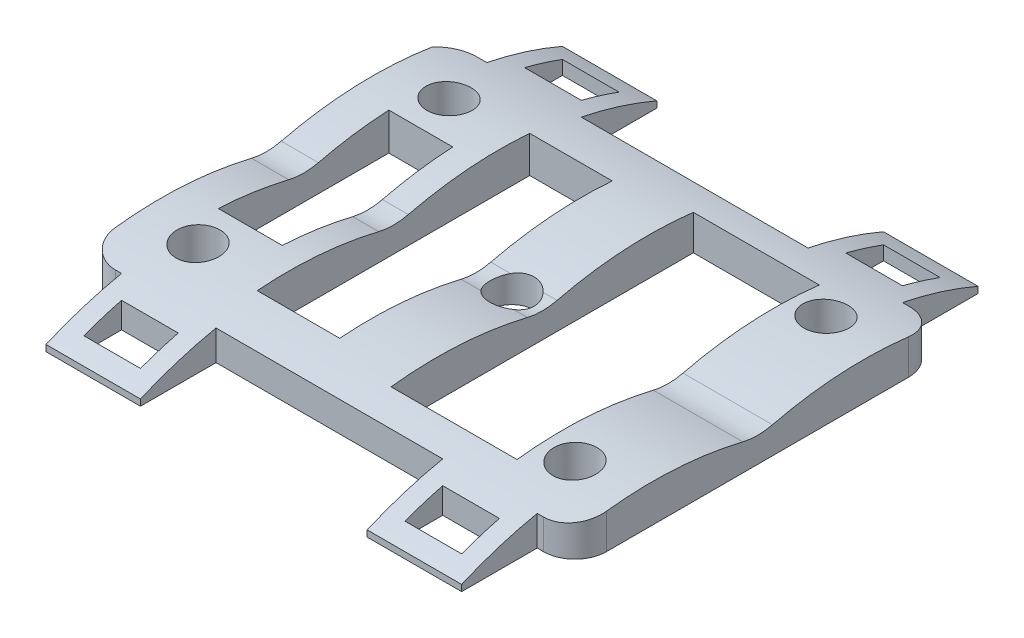
SolidWorks part; units mm, degrees
ref_plane "Front Plane" through (0, 0, 0) normal (0, 0, 1) x (1, 0, 0)
ref_plane "Top Plane" through (0, 0, 0) normal (0, 1, 0) x (1, 0, 0)
ref_plane "Right Plane" through (0, 0, 0) normal (1, 0, 0) x (0, 0, -1)
sketch "Sketch1" plane through (0, 0, 0) normal (0, 1, 0) x (1, 0, 0)
  line L0 (-33, -29) -> (-33, -41) construction
  line L5 (-33, -41) -> (-18, -41) construction
  line L6 (-18, -29) -> (-18, -41) construction
  line L7 (18, -29) -> (18, -41) construction
  line L8 (33, -41) -> (18, -41) construction
  line L9 (33, -29) -> (33, -41) construction
  line L10 (18, 29) -> (18, 41) construction
  line L11 (33, 41) -> (18, 41) construction
  line L12 (33, 29) -> (33, 41) construction
  line L13 (-33, 29) -> (-33, 41) construction
  line L14 (-33, 41) -> (-18, 41) construction
  line L15 (-18, 29) -> (-18, 41) construction
  line L16 (-34.5218, 29) -> (-33, 29) construction
  line L17 (-33, 29) -> (-18, 29) construction
  line L18 (-18, 29) -> (18, 29) construction
  line L19 (18, 29) -> (33, 29) construction
  line L20 (33, 29) -> (34, 29) construction
  line L21 (-34, -29) -> (-33, -29) construction
  line L34 (-18, -29) -> (-33, -29) construction
  line L35 (-18, -29) -> (18, -29) construction
  line L36 (33, -29) -> (18, -29) construction
  line L38 (33, -29) -> (34, -29) construction
  line L40 (-33, -29) -> (-33, -41)
  line L44 (-33, -41) -> (-18, -41)
  line L45 (-18, -29) -> (-18, -41)
  line L49 (18, -29) -> (18, -41)
  line L60 (33, -41) -> (18, -41)
  line L94 (33, -29) -> (33, -41)
  line L95 (18, 29) -> (18, 41)
  line L96 (33, 41) -> (18, 41)
  line L97 (33, 29) -> (33, 41)
  line L98 (-33, 29) -> (-33, 41)
  line L99 (-33, 41) -> (-18, 41)
  line L100 (-18, 29) -> (-18, 41)
  line L101 (-34.5218, 29) -> (-33, 29)
  line L102 (-33, 29) -> (-18, 29)
  line L103 (-18, 29) -> (18, 29)
  line L104 (18, 29) -> (33, 29)
  line L105 (33, 29) -> (34, 29)
  line L106 (-34, -29) -> (-33, -29)
  line L107 (-18, -29) -> (-33, -29)
  line L108 (-18, -29) -> (18, -29)
  line L109 (33, -29) -> (18, -29)
  line L110 (33, -29) -> (34, -29)
  line L111 (-39, -24) -> (-39, 26.2238)
  line L112 (39, -24) -> (39, 24)
  line L113 (-30, -32) -> (-30, -38) construction
  line L114 (-30, -38) -> (-21, -38) construction
  line L115 (-21, -32) -> (-21, -38) construction
  line L116 (-30, -32) -> (-21, -32) construction
  line L117 (21, -32) -> (21, -38) construction
  line L118 (30, -38) -> (21, -38) construction
  line L119 (30, -32) -> (21, -32) construction
  line L120 (30, -32) -> (30, -38) construction
  line L121 (-30, 32) -> (-21, 32) construction
  line L122 (-30, 32) -> (-30, 38) construction
  line L123 (-30, 38) -> (-21, 38) construction
  line L124 (-21, 32) -> (-21, 38) construction
  line L125 (21, 32) -> (21, 38) construction
  line L126 (30, 32) -> (21, 32) construction
  line L127 (30, 32) -> (30, 38) construction
  line L128 (30, 38) -> (21, 38) construction
  line L129 (-30, -32) -> (-30, -38)
  line L130 (-30, -38) -> (-21, -38)
  line L131 (-21, -32) -> (-21, -38)
  line L132 (-30, -32) -> (-21, -32)
  line L133 (21, -32) -> (21, -38)
  line L134 (30, -38) -> (21, -38)
  line L135 (30, -32) -> (21, -32)
  line L136 (30, -32) -> (30, -38)
  line L137 (-30, 32) -> (-21, 32)
  line L138 (-30, 32) -> (-30, 38)
  line L139 (-30, 38) -> (-21, 38)
  line L140 (-21, 32) -> (-21, 38)
  line L141 (21, 32) -> (21, 38)
  line L142 (30, 32) -> (21, 32)
  line L143 (30, 32) -> (30, 38)
  line L144 (30, 38) -> (21, 38)
  arc A0 (-34.5218, 29) -> (-39.3044, 25.4583) centre (-34.5218, 24) ccw construction
  arc A1 (39, 24) -> (34, 29) centre (34, 24) ccw construction
  arc A2 (-39, -24) -> (-34, -29) centre (-34, -24) ccw construction
  arc A3 (34, -29) -> (39, -24) centre (34, -24) ccw construction
  arc A6 (-34.5218, 29) -> (-39, 26.2238) centre (-34.5218, 24) ccw
  arc A7 (39, 24) -> (34, 29) centre (34, 24) ccw
  arc A8 (-39, -24) -> (-34, -29) centre (-34, -24) ccw
  arc A9 (34, -29) -> (39, -24) centre (34, -24) ccw
extrude "Boss-Extrude1" add sketch "Sketch1" along normal blind 8 contours L44 | L110 A9 L112 A7 L105 L104 L103 L102 L101 A6 L111 A8 L106 L107 L108 L109 | L45 L107 L40 L44 L129 L132 L131 L130 | L94 L109 L49 L60 L135 L136 L134 L133 | L95 L104 L97 L96 L144 L143 L142 L141 | L98 L102 L100 L99 L140 L137 L138 L139 region at (-25.5, 0, 29.1921) region at (-0.0153, 0, -0.011) region at (25.5, 0, 29.1921) region at (-32.8079, 0, -35) region at (18.1921, 0, -35)
sketch "Sketch7" plane through (0, 0, 0) normal (0, -1, 0) x (1, 0, 0)
  circle A0 centre (-29.9289, 19.9289) radius 3.5
  circle A1 centre (29.9289, 19.9289) radius 3.5
  circle A2 centre (-29.9289, -19.9289) radius 3.5
  circle A3 centre (29.9289, -19.9289) radius 3.5
  circle A4 centre (-29.9289, 19.9289) radius 2.5 construction
  circle A5 centre (0, 0) radius 3.5
  dimension "D1" = 1
extrude "Cut-Extrude6" cut sketch "Sketch7" against normal through all
sketch "Sketch8" plane through (0, 0, 0) normal (0, -1, 0) x (1, 0, 0)
  line L0 (-23.942, 12.539) -> (-32.0968, -12.539) construction
  line L1 (-23.942, 12.539) -> (-32.0968, 12.539) construction
  line L2 (-23.942, 12.539) -> (-23.942, -12.539) construction
  line L3 (-23.942, -12.539) -> (-32.0968, -12.539) construction
  line L4 (-32.0968, 12.539) -> (-32.0968, -12.539) construction
  line L5 (-23.942, 12.539) -> (-32.0968, -12.539) construction
  line L6 (-23.942, -12.539) -> (-32.0968, 12.539) construction
  line L7 (5.7951, -23) -> (23.7951, 23) construction
  line L8 (-6.7226, 20.6351) -> (-17.8204, 20.6351) construction
  line L9 (-6.7226, 20.6351) -> (-6.7226, -20.6351) construction
  line L10 (-6.7226, -20.6351) -> (-17.8204, -20.6351) construction
  line L11 (-17.8204, 20.6351) -> (-17.8204, -20.6351) construction
  line L12 (-6.7226, 20.6351) -> (-17.8204, -20.6351) construction
  line L13 (-6.7226, -20.6351) -> (-17.8204, 20.6351) construction
  line L14 (23.7951, 23) -> (5.7951, 23) construction
  line L15 (23.7951, 23) -> (23.7951, -23) construction
  line L16 (23.7951, -23) -> (5.7951, -23) construction
  line L17 (5.7951, 23) -> (5.7951, -23) construction
  line L18 (23.7951, 23) -> (5.7951, -23) construction
  line L19 (23.7951, -23) -> (5.7951, 23) construction
  line L20 (24.7951, -24) -> (4.7951, -24)
  line L21 (4.7951, 24) -> (4.7951, -24)
  line L22 (24.7951, 24) -> (4.7951, 24)
  line L23 (24.7951, 24) -> (24.7951, -24)
  line L24 (-5.7226, -21.6351) -> (-18.8204, -21.6351)
  line L25 (-18.8204, 21.6351) -> (-18.8204, -21.6351)
  line L26 (-5.7226, 21.6351) -> (-18.8204, 21.6351)
  line L27 (-5.7226, 21.6351) -> (-5.7226, -21.6351)
  line L28 (-22.942, -13.539) -> (-33.0968, -13.539)
  line L29 (-33.0968, 13.539) -> (-33.0968, -13.539)
  line L30 (-22.942, 13.539) -> (-33.0968, 13.539)
  line L31 (-22.942, 13.539) -> (-22.942, -13.539)
  point P0 (-28.0194, 0)
  point P8 (-12.2715, 0)
  point P15 (14.7951, 0)
  dimension "D1" = 1
extrude "Cut-Extrude7" cut sketch "Sketch8" against normal through all
sketch "Sketch9" plane through (-39, 0, 0) normal (-1, 0, 0) x (0, 0, 1)
  line L0 (-41, 8) -> (-41, 0) construction
  line L1 (0, 0) -> (0, 8) construction
  line L2 (24, 8) -> (-26.2238, 8) construction
  line L3 (-29, 0) -> (-41, 0) construction
  line L4 (-41, 1) -> (-41, 8)
  line L5 (-41, 8) -> (41, 8)
  line L6 (41, 8) -> (41, 1)
  arc A0 (-41, 1) -> (-2.3528, 4.2807) centre (-16.7625, -55.2455) cw
  arc A1 (41, 1) -> (2.3528, 4.2807) centre (16.7625, -55.2455) ccw
  arc A2 (-2.3528, 4.2807) -> (2.3528, 4.2807) centre (0, 14) ccw
  point P12 (-16.7625, 6)
  point P15 (0, 3.6615)
  point P18 (0, 4)
  dimension "D1" = 10
  dimension "D2" = 1
  dimension "D3" = 4
  dimension "D4" = 2
extrude "Cut-Extrude8" cut sketch "Sketch9" against normal through all
